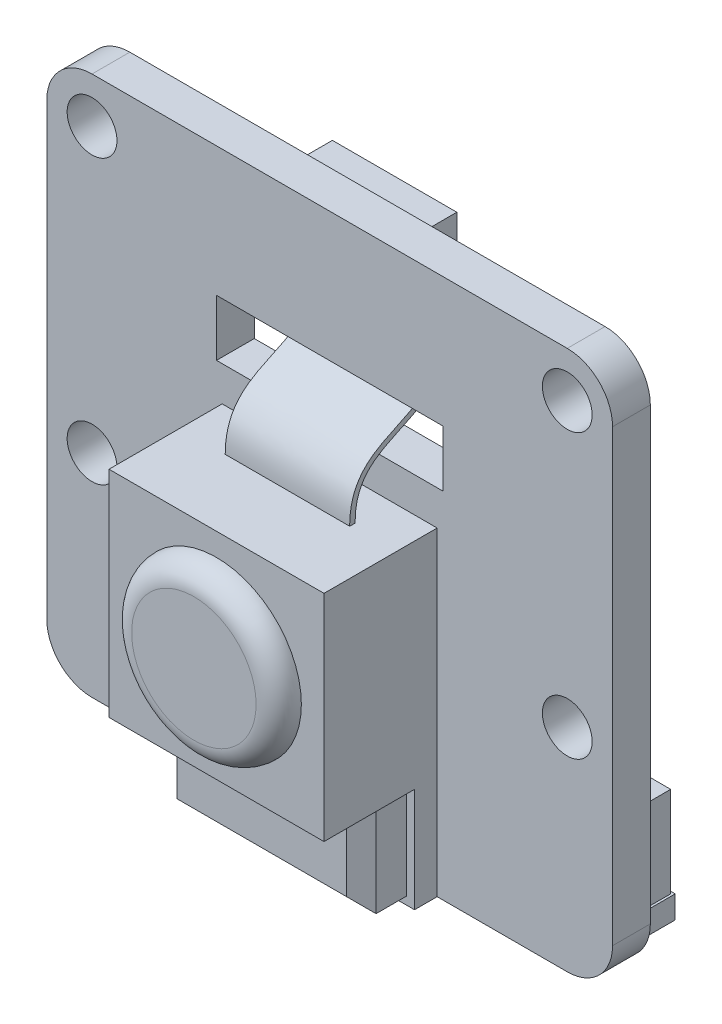
SolidWorks part; units mm, degrees
ref_plane "Plan de face" through (0, 0, 0) normal (0, 0, 1) x (1, 0, 0)
ref_plane "Plan de dessus" through (0, 0, 0) normal (0, 1, 0) x (1, 0, 0)
ref_plane "Plan de droite" through (0, 0, 0) normal (1, 0, 0) x (0, 0, -1)
sketch "Sketch1" plane through (0, 0, 0) normal (0, 0, 1) x (1, 0, 0)
  line L0 (-10.5, 9.93) -> (-10.5, -2.57) construction
  line L1 (-10.5, -11.93) -> (10.5, -11.93)
  line L2 (-12.5, -9.93) -> (-12.5, 9.93)
  line L3 (-10.5, 11.93) -> (10.5, 11.93)
  line L4 (12.5, -9.93) -> (12.5, 9.93)
  line L5 (-12.5, -11.93) -> (12.5, 11.93) construction
  line L6 (-12.5, 11.93) -> (12.5, -11.93) construction
  line L7 (-10.5, -2.57) -> (10.5, -2.57) construction
  line L8 (10.5, -2.57) -> (10.5, 9.93) construction
  line L9 (10.5, 9.93) -> (-10.5, 9.93) construction
  line L10 (0, 0) -> (0, 9.93) construction
  line L12 (-5, 3.72) -> (5, 3.72)
  line L13 (-5, 3.72) -> (-5, 6.21)
  line L14 (-5, 6.21) -> (5, 6.21)
  line L15 (5, 3.72) -> (5, 6.21)
  line L16 (-5, 3.72) -> (5, 6.21) construction
  line L17 (-5, 6.21) -> (5, 3.72) construction
  arc A0 (-10.5, -11.93) -> (-12.5, -9.93) centre (-10.5, -9.93) cw
  arc A1 (10.5, -11.93) -> (12.5, -9.93) centre (10.5, -9.93) ccw
  arc A2 (10.5, 11.93) -> (12.5, 9.93) centre (10.5, 9.93) cw
  arc A3 (-12.5, 9.93) -> (-10.5, 11.93) centre (-10.5, 9.93) cw
  circle A4 centre (-10.5, 9.93) radius 1.1
  circle A5 centre (10.5, 9.93) radius 1.1
  circle A8 centre (-10.5, -2.57) radius 1.1
  circle A9 centre (10.5, -2.57) radius 1.1
  point P0 (0, 0)
  point P26 (0, 4.965)
  dimension "D3" = 2
  dimension "D4" = 2.2
  dimension "D5" = 12.5
  dimension "D1" = 25
  dimension "D2" = 23.86
  dimension "D6" = 10
  dimension "D7" = 2.49
extrude "Boss-Extrude1" add sketch "Sketch1" along normal blind 1.67
sketch "Sketch2" plane through (0, 0, 1.67) normal (0, 0, 1) x (1, 0, 0)
  line L0 (-10.5, -2.57) -> (10.5, -2.57) construction
  line L2 (-4.75, -7.32) -> (4.75, -7.32)
  line L3 (-4.75, -7.32) -> (-4.75, 2.18)
  line L4 (-4.75, 2.18) -> (4.75, 2.18)
  line L5 (4.75, -7.32) -> (4.75, 2.18)
  line L6 (-4.75, -7.32) -> (4.75, 2.18) construction
  line L7 (-4.75, 2.18) -> (4.75, -7.32) construction
  point P4 (0, -2.57)
  dimension "D1" = 9.5
extrude "Boss-Extrude2" add sketch "Sketch2" along normal blind 5
sketch "Sketch3" plane through (0, 0, 6.67) normal (0, 0, 1) x (1, 0, 0)
  line L0 (-4.75, 2.18) -> (4.75, -7.32) construction
  circle A0 centre (0, -2.57) radius 3.75
  dimension "D1" = 7.5
extrude "Boss-Extrude3" add sketch "Sketch3" along normal blind 1
fillet "Fillet1" radius 1 1 edges at (3.75, -2.57, 7.67)
sketch "Sketch4" plane through (0, 0, 1.67) normal (0, 0, 1) x (1, 0, 0)
  line L0 (4.75, -7.32) -> (4.75, 2.18) construction
  line L1 (-4.75, -7.32) -> (4.75, -7.32)
  line L2 (-4.75, -7.32) -> (-4.75, -11.93)
  line L3 (-4.75, -11.93) -> (4.75, -11.93)
  line L4 (4.75, -7.32) -> (4.75, -11.93)
  line L5 (-10.5, -11.93) -> (10.5, -11.93) construction
extrude "Boss-Extrude4" add sketch "Sketch4" along normal blind 1
sketch "Sketch5" plane through (0, 0, 2.67) normal (0, 0, 1) x (1, 0, 0)
  line L0 (-4.75, -7.32) -> (4.75, -11.93) construction
  line L1 (4.75, -11.93) -> (4.75, -7.32) construction
  line L2 (-4.4, -11.58) -> (4.4, -11.58)
  line L3 (-4.4, -11.58) -> (-4.4, -7.67)
  line L4 (-4.4, -7.67) -> (4.4, -7.67)
  line L5 (4.4, -11.58) -> (4.4, -7.67)
  line L6 (-4.4, -11.58) -> (4.4, -7.67) construction
  line L7 (-4.4, -7.67) -> (4.4, -11.58) construction
  line L8 (-4.75, -7.32) -> (4.75, -7.32) construction
  point P4 (0, -9.625)
  dimension "D1" = 0.35
  dimension "D2" = 0.35
extrude "Boss-Extrude5" add sketch "Sketch5" along normal blind 2
chamfer "Chamfer1" distance 0.65 angle 45 4 edges at (0, -11.58, 4.67) (-4.4, -9.625, 4.67) (0, -7.67, 4.67) (4.4, -9.625, 4.67)
sketch "Sketch6" plane through (0, 0, 0) normal (1, 0, 0) x (0, 0, -1)
  line L0 (-6.67, 2.18) -> (-1.67, 2.18) construction
  line L1 (0, 2.18) -> (6.6547, 2.18) construction
  line L5 (-3.2983, 2.18) -> (-3.5348, 2.18)
  line L6 (0, 11.83) -> (1.2, 11.83)
  line L7 (1.2, 11.83) -> (1.2, 7.33)
  line L8 (1.2, 7.33) -> (1.029, 7.33)
  line L9 (0, -9.93) -> (0, 9.93) construction
  line L10 (0, 7.33) -> (0, 11.83)
  line L11 (0.7925, 7.33) -> (0, 7.33)
  line L12 (0, 9.93) -> (0, 11.93) construction
  line L13 (-1.67, 11.93) -> (0, 11.93) construction
  spline S0 degree 3 poles (-3.5348, 2.18) (-3.5348, 4.9449) (-0.4706, 4.5342) (0.7303, 6.8492) (0.7925, 7.2918) (0.7925, 7.33) knots 0 0 0 0 0.784107 0.986087 1 1 1 1
  spline S1 degree 1 poles (-3.2983, 2.18) (1.029, 7.33) knots 0 0 1 1 construction
  spline S2 degree 3 poles (-3.2983, 2.18) (-3.2983, 2.3697) (-3.2689, 2.7748) (-3.1117, 3.3672) (-2.768, 3.9096) (-2.1615, 4.3625) (-1.4104, 4.7257) (-0.6057, 5.0993) (0.1658, 5.6014) (0.6823, 6.2651) (0.9101, 6.7716) (0.9863, 7.0415) (1.0149, 7.1726) (1.029, 7.2809) (1.029, 7.33) knots 0 0 0 0 0.0625 0.125 0.25 0.375 0.5 0.625 0.75 0.875 0.9375 0.96875 0.984375 1 1 1 1
  point P18 (0.9829, 9.4496)
  point P19 (0.9829, 9.4496)
  dimension "D1" = 1.2
  dimension "D2" = 4.5
  dimension "D3" = 0.1
extrude "Boss-Extrude6" add sketch "Sketch6" along normal offset from surface 2 and the other way offset from surface 2 up to face at (4.75, -5.69, 3.67) other way up to face at (-4.75, -5.69, 3.67)
sketch "Sketch7" plane through (0, 0, 0) normal (0, 0, -1) x (-1, 0, 0)
  line L0 (0, -11.93) -> (0, 0) construction
  line L1 (10.5, -11.93) -> (-10.5, -11.93) construction
  line L3 (-11, -10.83) -> (11, -10.83)
  line L4 (-11, -10.83) -> (-11, -11.83)
  line L5 (-11, -11.83) -> (11, -11.83)
  line L6 (11, -10.83) -> (11, -11.83)
  line L7 (-11, -10.83) -> (11, -11.83) construction
  line L8 (-11, -11.83) -> (11, -10.83) construction
  point P5 (0, -11.33)
  dimension "D1" = 0.1
  dimension "D2" = 1
  dimension "D3" = 22
extrude "Boss-Extrude7" add sketch "Sketch7" along normal blind 2.6
sketch "Sketch9" plane through (0, 0, 0) normal (0, 0, -1) x (-1, 0, 0)
  line L0 (11, -10.83) -> (-11, -10.83) construction
  line L1 (-10.9, -10.83) -> (10.9, -10.83)
  line L2 (-10.9, -10.83) -> (-10.9, -6.83)
  line L3 (-10.9, -6.83) -> (10.9, -6.83)
  line L4 (10.9, -10.83) -> (10.9, -6.83)
  line L5 (-11, -10.83) -> (-11, -11.83) construction
  line L6 (11, -11.83) -> (11, -10.83) construction
  dimension "D1" = 0.1
  dimension "D2" = 0.1
  dimension "D3" = 4
extrude "Boss-Extrude8" add sketch "Sketch9" along normal offset from surface (2.5 mm away) 0.1 up to face at (0, -11.33, -2.6)
